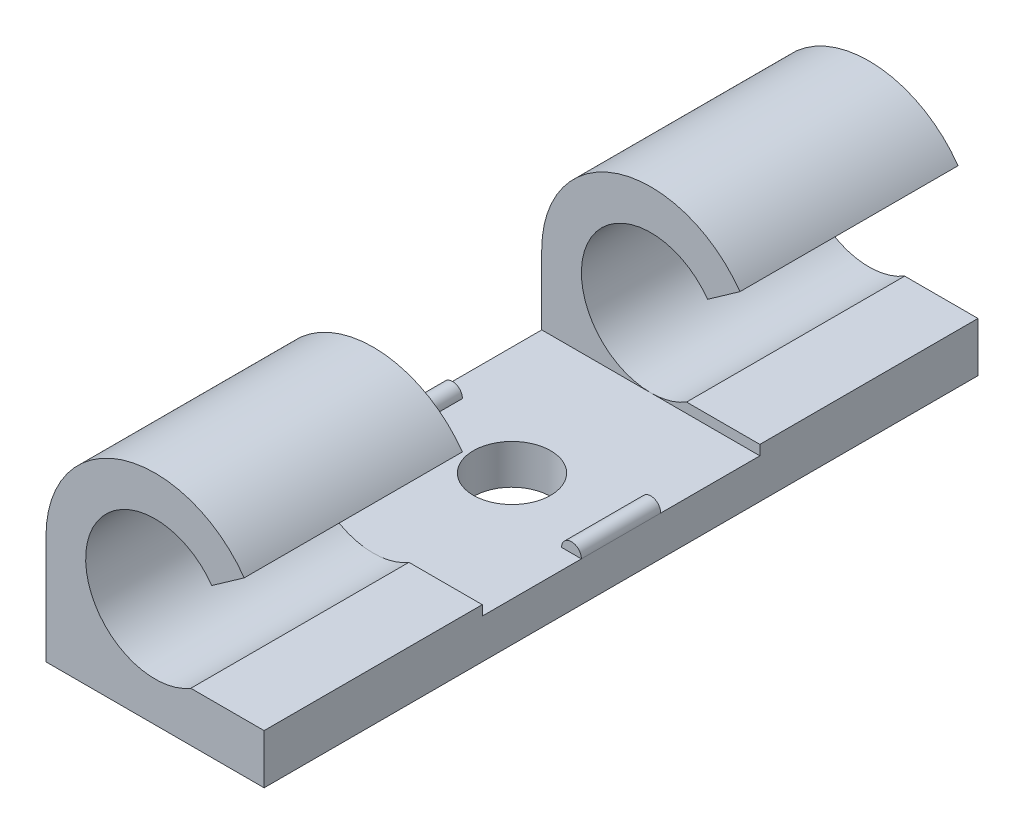
SolidWorks part; units mm, degrees
ref_plane "Plano frontal" through (0, 0, 0) normal (0, 0, 1) x (1, 0, 0)
ref_plane "Plano superior" through (0, 0, 0) normal (0, 1, 0) x (1, 0, 0)
ref_plane "Plano direito" through (0, 0, 0) normal (1, 0, 0) x (0, 0, -1)
sketch "Esboço1" plane through (0, 0, 0) normal (0, 0, 1) x (1, 0, 0)
  line L0 (-5.5, 0) -> (5.5, 0)
  line L1 (-5.5, 5.5) -> (5.5, 5.5)
  line L2 (-5.5, 5.5) -> (-5.5, -5.5)
  line L3 (-5.5, -5.5) -> (5.5, -5.5)
  line L4 (5.5, 5.5) -> (5.5, -5.5)
  line L5 (-5.5, 5.5) -> (5.5, -5.5) construction
  line L6 (-5.5, -5.5) -> (5.5, 5.5) construction
  circle A0 centre (0, 0) radius 5.5
  circle A2 centre (0, 0) radius 3.5
  point P0 (0, 0)
  point P12 (0, 0)
  dimension "D3" = 7
  dimension "D1" = 11
  dimension "D2" = 11
extrude "Ressalto-extrusão1" add sketch "Esboço1" along normal blind 11 contours A0 L2 L3 | A0 L3 L4 | A2 L0 A0 | A2 L0 A0 region at (0, 3.623, 0) region at (4.5, -0.123, 0) region at (4.2715, -4.2715, 0) region at (-4.2715, -4.2715, 0)
sketch "Esboço2" plane through (0, 0, 11) normal (0, 0, 1) x (1, 0, 0)
  line L0 (5.5, 0) -> (5.5, -5.5) construction
  line L1 (-5.5, -5.5) -> (5.5, -5.5)
  line L2 (-5.5, -5.5) -> (-5.5, -3.5)
  line L3 (-5.5, -3.5) -> (5.5, -3.5)
  line L4 (5.5, -5.5) -> (5.5, -3.5)
  line L5 (-5.5, -5.5) -> (5.5, -3.5) construction
  line L6 (-5.5, -3.5) -> (5.5, -5.5) construction
  circle A0 centre (0, 0) radius 3.5 construction
  point P4 (0, -4.5)
extrude "Ressalto-extrusão2" add sketch "Esboço2" along normal blind 7
sketch "Esboço3" plane through (0, 0, 18) normal (0, 0, 1) x (1, 0, 0)
  line L0 (5.5, -3.5) -> (0, -3.5) construction
  line L1 (5.5, -3.5) -> (0, -3.5) construction
  line L2 (0, 0) -> (0, -0.723) construction
  arc A0 (5.5, -3.5) -> (4.5, -3.5) centre (5, -3.5) ccw
  arc A1 (4.5, -3.5) -> (5.5, -3.5) centre (5, -3.5) ccw construction
  arc A2 (-5.5, -3.5) -> (-4.5, -3.5) centre (-5, -3.5) cw
  line M5 (5.5, -3.5) -> (-5.5, -3.5)
  dimension "D1" = 1
extrude "Ressalto-extrusão3" add sketch "Esboço3" against normal blind 2 contours A0 M5 | A2 M5 region at (5, -3.2878, 18) region at (-5, -3.2878, 18)
mirror "Espelhar1" about plane through (0, 0, 18) normal (0, 0, -1) of "Ressalto-extrusão2", "Ressalto-extrusão1", "Ressalto-extrusão3"
sketch "Esboço4" plane through (0, -3.5, 0) normal (0, 1, 0) x (1, 0, 0)
  line L0 (0, -11) -> (0, -18) construction
  line L2 (-4.5, -18) -> (4.5, -18) construction
  line L3 (-4.5, -16) -> (-4.5, -20) construction
  line L4 (4.5, -16) -> (4.5, -20) construction
  line L5 (-5.5, -11) -> (5.5, -11) construction
  circle A0 centre (0, -18) radius 1.95
  dimension "D1" = 3.9
extrude "Corte-extrusão1" cut sketch "Esboço4" against normal blind 2
sketch "Esboço5" plane through (0, 0, 36) normal (0, 0, 1) x (1, 0, 0)
  line L0 (5.5, -3) -> (1.8028, -3)
  line L1 (5.5, 0) -> (5.5, -5.5) construction
  line L2 (-5.5, -5.5) -> (5.5, -5.5) construction
  line L3 (5.2915, 1.5) -> (2.1292, 1.5) construction
  line L4 (2.1292, 1.5) -> (4.4963, 3.1675)
  line L5 (0, 0) -> (2.1292, 1.5) construction
  circle A0 centre (0, 0) radius 3.5 construction
  arc A1 (5.5, 0) -> (-5.5, 0) centre (0, 0) ccw construction
  circle M4 centre (0, 0) radius 3.5
  line M6 (5.5, -5.5) -> (5.5, 0)
  arc M7 (5.5, 0) -> (-5.5, 0) centre (0, 0) ccw
  dimension "D1" = 2.5
  dimension "D2" = 4.5
  dimension "D3" = 35.164
extrude "Corte-extrusão2" cut sketch "Esboço5" against normal through all contours L4 L0 M4 M6 M7 region at (4.2427, -0.3765, 36)
sketch "Esboço6" plane through (0, -3.5, 0) normal (0, 1, 0) x (1, 0, 0)
  circle A0 centre (0, -18) radius 3.8 construction
  dimension "D1" = 7.6
equation "\"D2@Esboço1\"=\"D1@Esboço1\""
equation "\"D1@Esboço1\"=\"D3@Esboço1\"+4"
